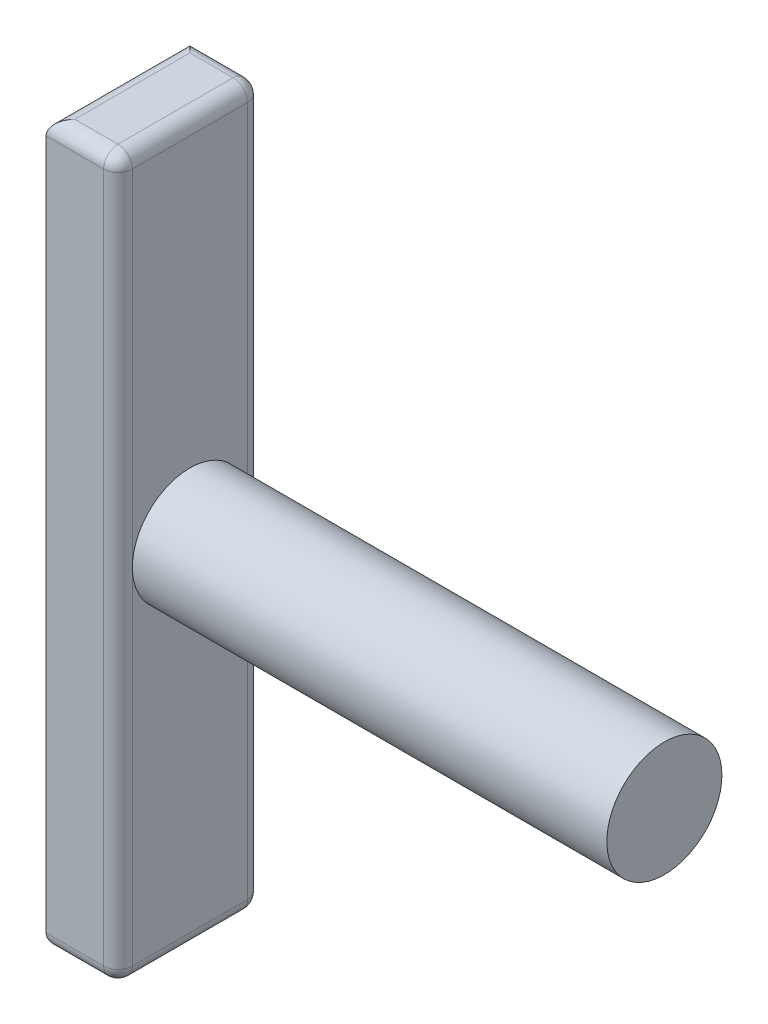
SolidWorks part; units mm, degrees
ref_plane "Front Plane" through (0, 0, 0) normal (0, 0, 1) x (1, 0, 0)
ref_plane "Top Plane" through (0, 0, 0) normal (0, 1, 0) x (1, 0, 0)
ref_plane "Right Plane" through (0, 0, 0) normal (1, 0, 0) x (0, 0, -1)
sketch "Sketch1" plane through (0, 0, 0) normal (1, 0, 0) x (0, 0, -1)
  line L1 (0, 0) -> (100, 0)
  line L2 (0, 0) -> (0, -500)
  line L3 (0, -500) -> (100, -500)
  line L4 (100, 0) -> (100, -500)
  dimension "D1" = 100
  dimension "D2" = 500
extrude "Boss-Extrude1" add sketch "Sketch1" along normal blind 50
fillet "Fillet1" radius 10 8 edges at (25, 0, -100) (25, 0, 0) (25, -500, -100) (25, -500, 0) (0, -500, -50) (50, -500, -50) (50, 0, -50) (0, 0, -50)
fillet "Fillet2" radius 10 6 edges at (47.0711, -497.0711, -97.0711) (47.0711, -2.9289, -97.0711) (47.0711, -2.9289, -2.9289) (47.0711, -497.0711, -2.9289) (50, -250, -100) (50, -250, 0)
sketch "Sketch2" plane through (50, 0, 0) normal (1, 0, 0) x (0, 0, -1)
  line L0 (10, -10) -> (10, -490) construction
  line L1 (90, -490) -> (90, -10) construction
  circle A0 centre (50, -250) radius 40
extrude "Boss-Extrude2" add sketch "Sketch2" along normal blind 330
ref_axis "Axis1" through (380, -250, -50) along (-1, 0, 0)
